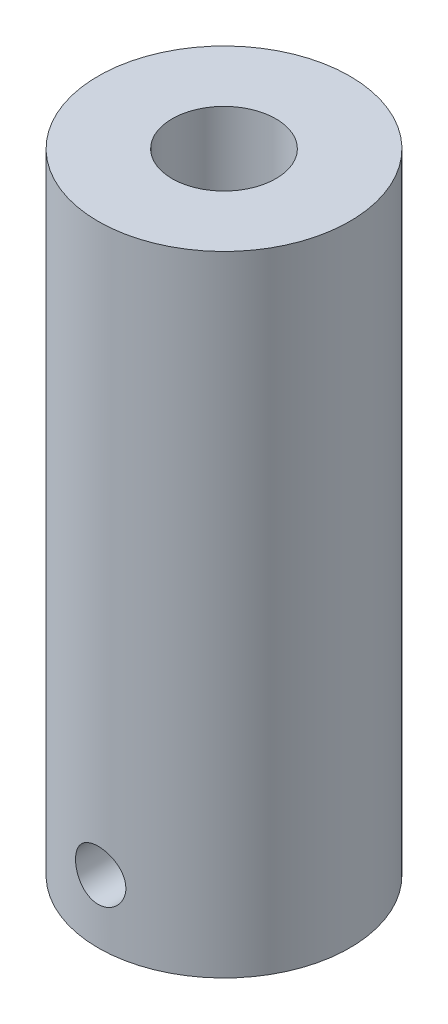
SolidWorks part; units mm, degrees
ref_plane "Front Plane" through (0, 0, 0) normal (0, 0, 1) x (1, 0, 0)
ref_plane "Top Plane" through (0, 0, 0) normal (0, 1, 0) x (1, 0, 0)
ref_plane "Right Plane" through (0, 0, 0) normal (1, 0, 0) x (0, 0, -1)
sketch "Croquis1" plane through (0, 0, 0) normal (0, 1, 0) x (1, 0, 0)
  circle A0 centre (0, 0) radius 2
  circle A1 centre (0, 0) radius 4
  dimension "D1" = 4
  dimension "D2" = 8
extrude "Saliente-Extruir1" add sketch "Croquis1" along normal blind 25.4 contours A0 | A1 A0 region at (0, 0, 0) region at (-3.8869, 0, 0)
sketch "Croquis2" plane through (0, 25.4, 0) normal (0, 1, 0) x (1, 0, 0)
  circle A1 centre (0, 0) radius 30
  dimension "D1" = 60
extrude "Saliente-Extruir2" add sketch "Croquis2" along normal blind 5 from surface starting at face at (0, 25.4, 4)
sketch "Croquis3" plane through (0, 30.4, 0) normal (0, 1, 0) x (1, 0, 0)
  circle A0 centre (0, 0) radius 10 construction
  circle A1 centre (0, 10) radius 2
  circle A2 centre (10, 0) radius 2
  circle A3 centre (0, -10) radius 2
  circle A4 centre (-10, 0) radius 2
  point P14 (0, 0)
  dimension "D1" = 20
  dimension "D2" = 4
  dimension "D5" = 20
  dimension "D4" = 10
  dimension "D3" = 4
extrude "Cortar-Extruir1" cut sketch "Croquis3" against normal blind 7.5
sketch "Croquis6" plane through (0, 0, 0) normal (0, 0, 1) x (1, 0, 0)
  circle A0 centre (0, 5) radius 0.8
  dimension "D1" = 1.6
  dimension "D2" = 5
sketch "Croquis7" plane through (0, 0, 0) normal (0, -1, 0) x (1, 0, 0)
  circle A0 centre (0, 0) radius 3.5
  dimension "D1" = 7
extrude "Cortar-Extruir3" cut sketch "Croquis7" against normal blind 3
sketch "Croquis8" plane through (0, 0, 0) normal (1, 0, 0) x (0, 0, -1)
  line L0 (-27.0724, 0) -> (-27.0724, 3)
  line L1 (-27.0724, 3) -> (35.6259, 3)
  line L2 (35.6259, 3) -> (35.6259, 0)
  line L3 (35.6259, 0) -> (-27.0724, 0)
  dimension "D1" = 3
extrude "Cortar-Extruir5" cut sketch "Croquis8" against normal mid plane 30
extrude "Cortar-Extruir6" cut sketch "Croquis1<3>" along normal blind 7.4 contours A0 region at (0, 0, 0)
sketch "Croquis1<3>" plane through (0, 0, 0) normal (0, 1, 0) x (1, 0, 0) same geometry as "Croquis1"
extrude "Cortar-Extruir7" cut sketch "Croquis6" along normal blind 10
sketch "Croquis10" plane through (0, 30.4, 0) normal (0, 1, 0) x (1, 0, 0)
  circle A0 centre (0, 0) radius 30
extrude "Cortar-Extruir8" cut sketch "Croquis10" against normal blind 7.4
sketch "Croquis11" plane through (0, 23, 0) normal (0, 1, 0) x (1, 0, 0)
  circle A0 centre (0, 0) radius 1.65
  dimension "D1" = 3.3
extrude "Cortar-Extruir9" cut sketch "Croquis11" against normal blind 10
